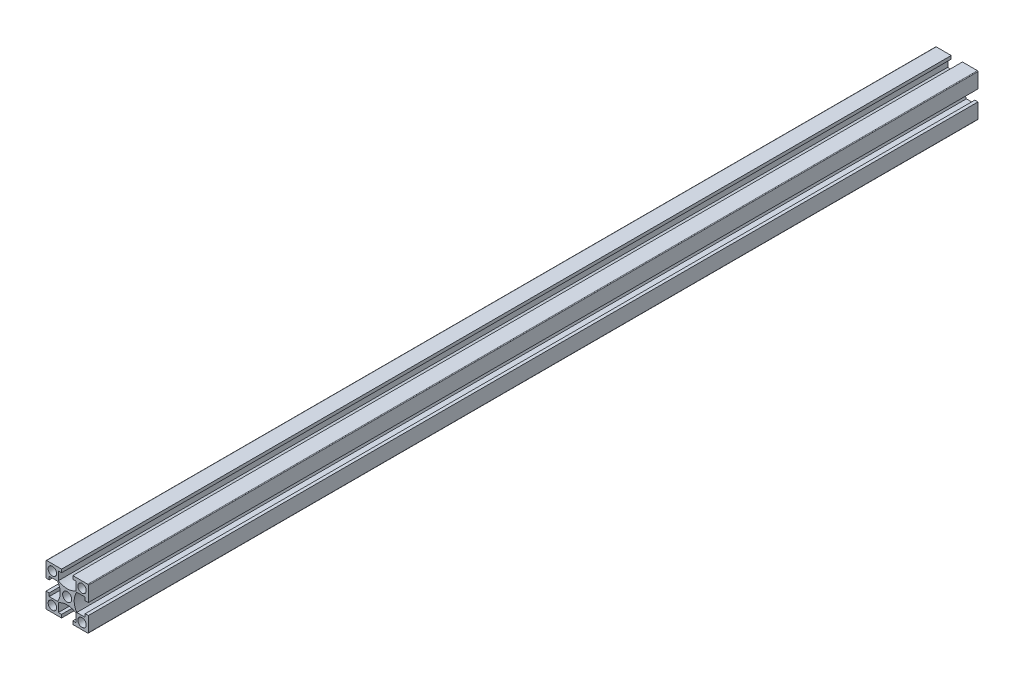
SolidWorks part; units mm, degrees
ref_plane "정면" through (0, 0, 0) normal (0, 0, 1) x (1, 0, 0)
ref_plane "윗면" through (0, 0, 0) normal (0, 1, 0) x (1, 0, 0)
ref_plane "우측면" through (0, 0, 0) normal (1, 0, 0) x (0, 0, -1)
sketch "스케치1" plane through (0, 0, 0) normal (0, 0, 1) x (1, 0, 0)
  line L0 (0, 32.0265) -> (0, -31.6588) construction
  line L1 (-10, 10) -> (-10, -10)
  line L2 (-10, 10) -> (10, 10)
  line L3 (-10, 2.65) -> (-8.5, 2.65)
  line L4 (13.6618, 0) -> (-11.6993, 0) construction
  line L5 (-8.5, 2.65) -> (-8.5, 4.15)
  line L6 (-8.5, 4.15) -> (-4.5032, 4.15)
  line L7 (-10, -2.65) -> (-8.5, -2.65)
  line L8 (-8.5, -2.65) -> (-8.5, -4.15)
  line L9 (-8.5, -4.15) -> (-4.5032, -4.15)
  line L10 (-10, -10) -> (10, -10)
  line L11 (10, 10) -> (10, -10)
  circle A0 centre (-7, 7) radius 2
  circle A1 centre (-7, -7) radius 2
  arc A2 (-4.5032, 4.15) -> (-4.5032, -4.15) centre (-11.0587, 0) cw
  circle A3 centre (0, 0) radius 2.15
  circle A4 centre (7, 7) radius 2
  circle A5 centre (7, -7) radius 2
  point P21 (-10, 0)
  point P23 (-3.3, 0)
  point P31 (0, -10)
  point P32 (0, 10)
  dimension "D3" = 4
  dimension "D9" = 6.7
  dimension "D10" = 4.3
  dimension "D11" = 7.7587
  dimension "D1" = 20
  dimension "D2" = 20
  dimension "D4" = 14
  dimension "D5" = 14
  dimension "D6" = 5.3
  dimension "D7" = 8.3
  dimension "D8" = 1.5
extrude "보스-돌출1" add sketch "스케치1" along normal blind 420 contours A0 | A4 | A3 | A5 | A1 | A2 L6 L5 L3 L1 L7 L8 L9 | L2 L11 L10 L1 region at (-6.6069, 0, 0) region at (-7, 7, 0) region at (-7, -7, 0) region at (0, 0, 0) region at (7, 7, 0) region at (7, -7, 0)
extrude "컷-돌출1" cut sketch "스케치1<3>" along normal up to next contours A2 L6 L5 L3 L1 L7 L8 L9 region at (-6.6069, 0, 0)
sketch "스케치1<3>" plane through (0, 0, 0) normal (0, 0, 1) x (1, 0, 0) same geometry as "스케치1"
pattern_circular "원형 패턴1" count 4 over 360 about axis through (0, 0, 420) along (0, 0, -1) of "컷-돌출1" reverse direction yes
fillet "필렛1" radius 0.3 4 edges at (10, -10, 210) (-10, -10, 210) (-10, 10, 210) (10, 10, 210)
